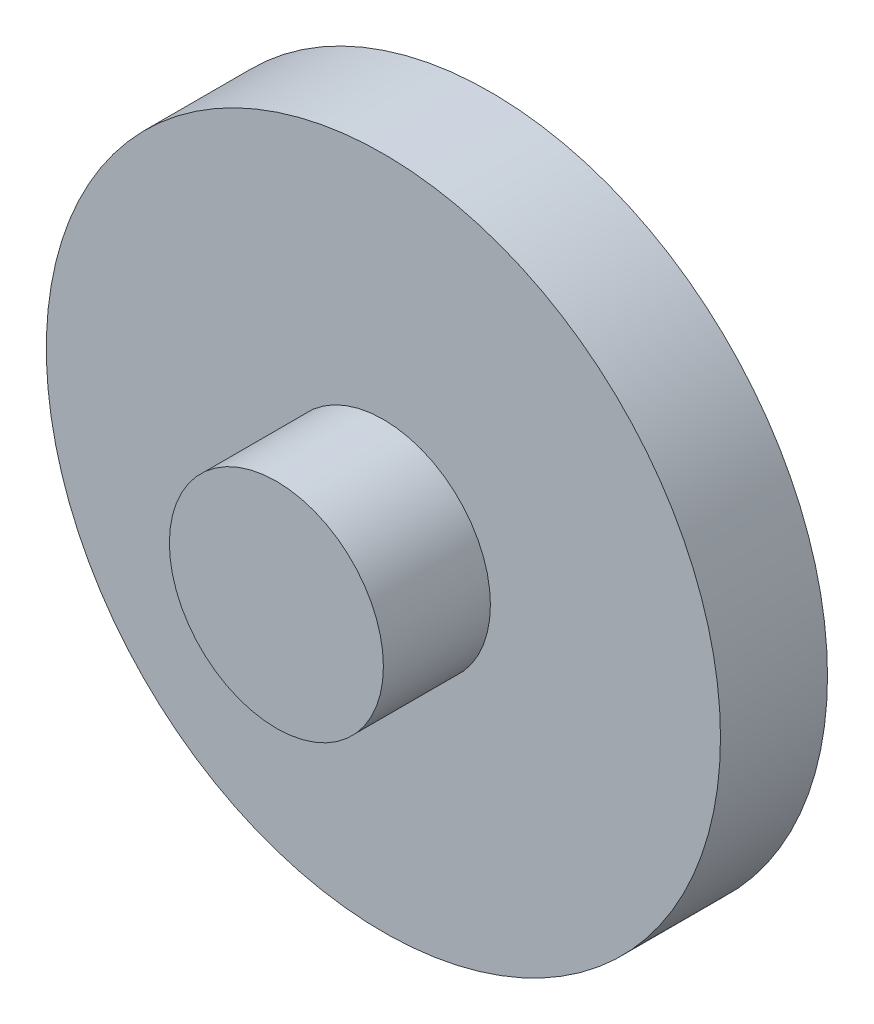
SolidWorks part; units mm, degrees
ref_plane "Front Plane" through (0, 0, 0) normal (0, 0, 1) x (1, 0, 0)
ref_plane "Top Plane" through (0, 0, 0) normal (0, 1, 0) x (1, 0, 0)
ref_plane "Right Plane" through (0, 0, 0) normal (1, 0, 0) x (0, 0, -1)
sketch "Sketch1" plane through (0, 0, 0) normal (0, 0, 1) x (1, 0, 0)
  circle A0 centre (0, 0) radius 15.75
  circle A1 centre (0, 0) radius 5
  dimension "D1" = 31.5
  dimension "D2" = 10
extrude "Boss-Extrude1" add sketch "Sketch1" along normal blind 5
extrude "Boss-Extrude2" add sketch "Sketch1<2>" along normal blind 10 contours A1
sketch "Sketch1<2>" plane through (0, 0, 0) normal (0, 0, 1) x (1, 0, 0) same geometry as "Sketch1"
